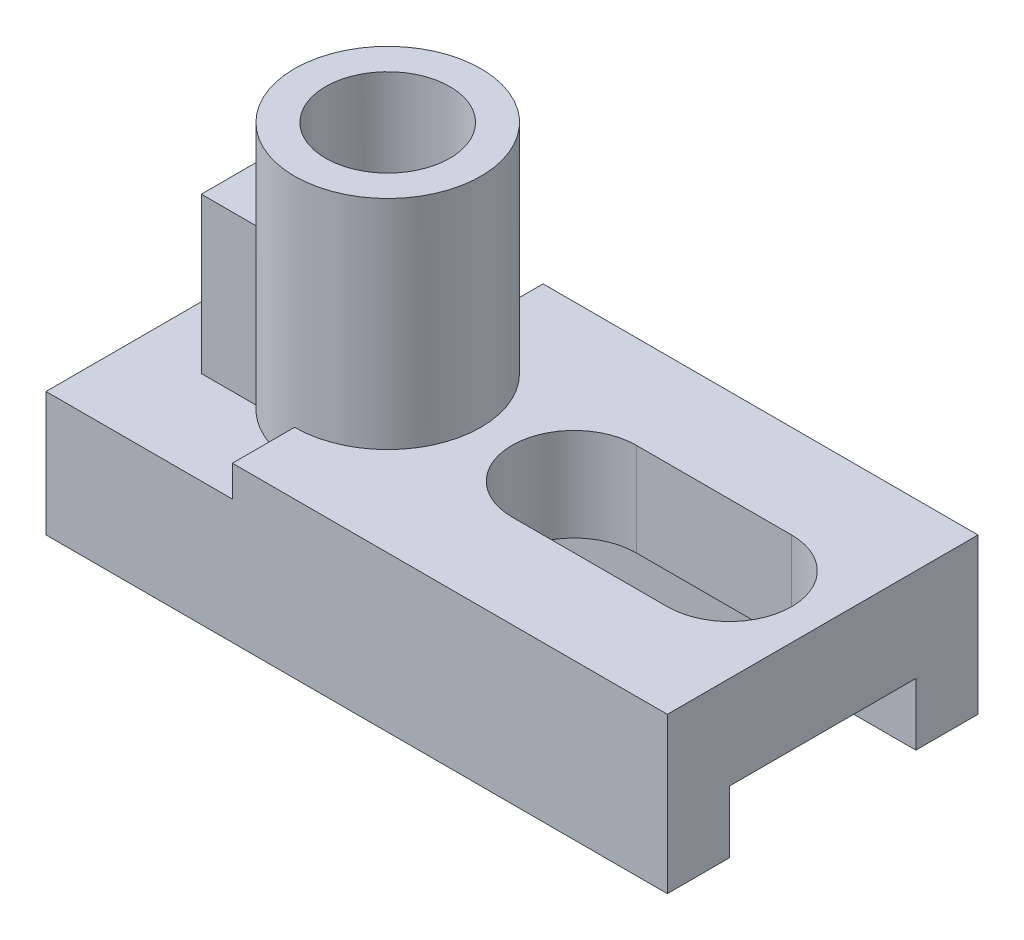
SolidWorks part; units mm, degrees
ref_plane "Front Plane" through (0, 0, 0) normal (0, 0, 1) x (1, 0, 0)
ref_plane "Top Plane" through (0, 0, 0) normal (0, 1, 0) x (1, 0, 0)
ref_plane "Right Plane" through (0, 0, 0) normal (1, 0, 0) x (0, 0, -1)
sketch "Sketch1" plane through (0, 0, 0) normal (0, 0, 1) x (1, 0, 0)
  line L0 (0, 0) -> (100, 0)
  line L1 (100, 0) -> (100, 25)
  line L2 (100, 25) -> (30, 25)
  line L3 (30, 25) -> (30, 20)
  line L4 (30, 20) -> (0, 20)
  line L5 (0, 20) -> (0, 0)
  dimension "D1" = 30
  dimension "D2" = 100
  dimension "D3" = 5
  dimension "D4" = 20
extrude "Boss-Extrude1" add sketch "Sketch1" along normal mid plane 50
sketch "Sketch2" plane through (0, 0, 0) normal (-1, 0, 0) x (0, 0, 1)
  line L0 (25, 0) -> (-25, 0) construction
  line L1 (-15, 0) -> (15, 0)
  line L2 (-15, 0) -> (-15, 10)
  line L3 (-15, 10) -> (15, 10)
  line L4 (15, 0) -> (15, 10)
  point P6 (0, 10)
  dimension "D1" = 30
  dimension "D2" = 10
extrude "Cut-Extrude1" cut sketch "Sketch2" against normal through all
sketch "Sketch3" plane through (0, 25, 0) normal (0, 1, 0) x (1, 0, 0)
  line L0 (30, -25) -> (30, 25) construction
  circle A0 centre (30, 0) radius 15
  circle A1 centre (30, 0) radius 10
  line M2 (30, 25) -> (30, -25)
  dimension "D1" = 20
  dimension "D2" = 30
extrude "Boss-Extrude2" add sketch "Sketch3" against normal up to surface (5 mm away) and the other way blind 35 up to face at (15, 20, 0)
extrude "Cut-Extrude2" cut sketch "Sketch3<2>" against normal through all contours A1 M2 | A1 M2 region at (25.7559, 25, 0) region at (34.2441, 25, 0)
sketch "Sketch3<2>" plane through (0, 25, 0) normal (0, 1, 0) x (1, 0, 0) same geometry as "Sketch3"
ref_plane "Plane1" through (10, 0, 0) normal (-1, 0, 0) x (0, 0, 1)
sketch "Sketch4" plane through (10, 0, 0) normal (-1, 0, 0) x (0, 0, 1)
  line L0 (25, 20) -> (-25, 20) construction
  line L1 (-10, 20) -> (10, 20)
  line L2 (-10, 20) -> (-10, 45)
  line L3 (-10, 45) -> (10, 45)
  line L4 (10, 20) -> (10, 45)
  point P6 (0, 45)
  dimension "D1" = 20
  dimension "D2" = 25
extrude "Boss-Extrude3" add sketch "Sketch4" against normal up to surface (8.8197 mm away) up to face at (15, 60, 0)
sketch "Sketch5" plane through (10, 0, 0) normal (-1, 0, 0) x (0, 0, 1)
  line L0 (-10, 45) -> (-10, 20) construction
  circle A0 centre (0, 32.5) radius 5
  point P6 (-10, 32.5)
  dimension "D1" = 10
extrude "Cut-Extrude3" cut sketch "Sketch5" against normal up to next
sketch "Sketch6" plane through (0, 25, 0) normal (0, 1, 0) x (1, 0, 0)
  line L0 (60, 0) -> (85, 0) construction
  line L1 (60, 10) -> (85, 10)
  line L2 (60, -10) -> (85, -10)
  arc A0 (60, 10) -> (60, -10) centre (60, 0) ccw
  arc A1 (85, -10) -> (85, 10) centre (85, 0) ccw
  circle A2 centre (30, 0) radius 10 construction
  point P3 (72.5, 0)
  dimension "D1" = 10
  dimension "D2" = 25
  dimension "D3" = 30
extrude "Cut-Extrude4" cut sketch "Sketch6" against normal up to next
